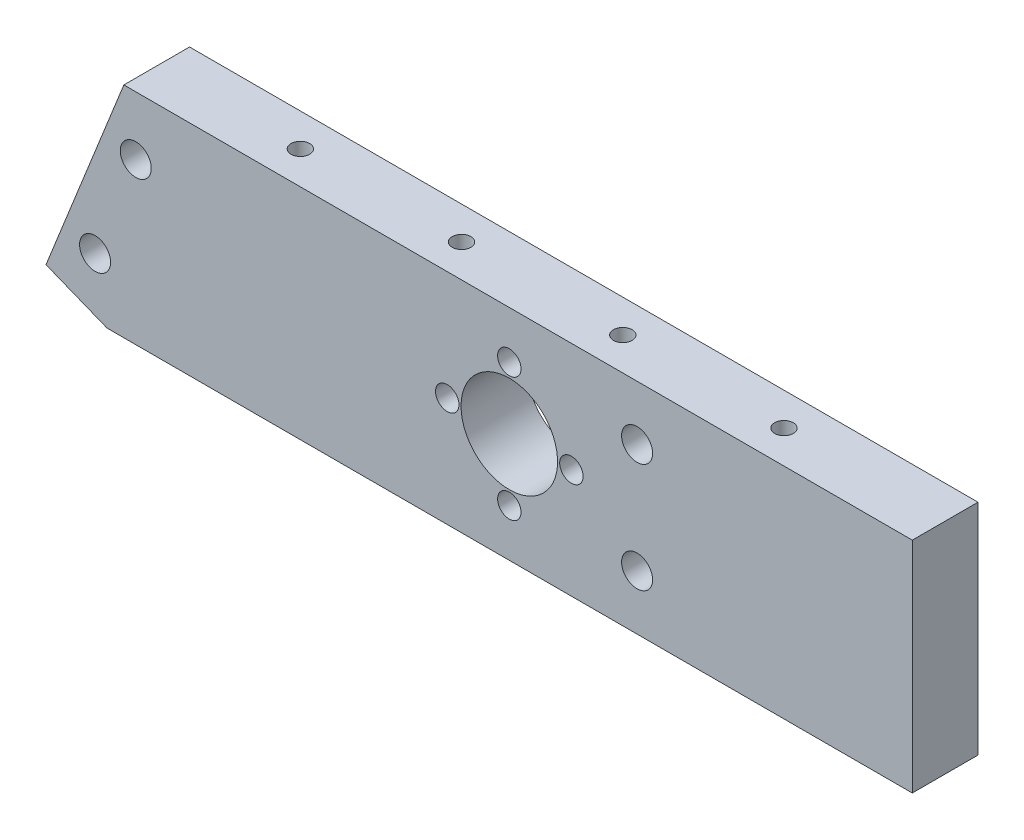
SolidWorks part; units mm, degrees
material "PE High Density"
ref_plane "Front Plane" through (0, 0, 0) normal (0, 0, 1) x (1, 0, 0)
ref_plane "Top Plane" through (0, 0, 0) normal (0, 1, 0) x (1, 0, 0)
ref_plane "Right Plane" through (0, 0, 0) normal (1, 0, 0) x (0, 0, -1)
sketch "Sketch1" plane through (0, 0, 0) normal (0, 0, 1) x (1, 0, 0)
  line L1 (-55.88, 15.875) -> (58.42, 15.875)
  line L2 (-55.88, 15.875) -> (-67.165, -12.3375)
  line L3 (-58.3213, -15.875) -> (58.42, -15.875)
  line L4 (58.42, 15.875) -> (58.42, -15.875)
  line L5 (18.525, 15.875) -> (18.525, -15.875) construction
  line L6 (58.42, 0) -> (-62.23, 0) construction
  line L7 (-62.23, 0) -> (-57.8081, -1.7687) construction
  line L10 (-50.7506, 15.875) -> (-62.7431, -14.1063) construction
  line L11 (-67.165, -12.3375) -> (-58.3213, -15.875)
  circle A0 centre (0, -9) radius 1.7
  circle A1 centre (-9, 0) radius 1.7
  circle A2 centre (0, 9) radius 1.7
  circle A3 centre (9, 0) radius 1.7
  arc A8 (-5.3578, -2.967) -> (-5.3172, -2.9531) centre (-6.35, 0) ccw construction
  circle A16 centre (0, 0) radius 7
  circle A17 centre (0, 0) radius 9 construction
  circle A18 centre (18.525, 7.9375) radius 2.2479
  circle A19 centre (18.525, -7.9375) radius 2.2479
  circle A20 centre (-54.1527, 7.3698) radius 2.2479
  circle A21 centre (-60.0485, -7.3698) radius 2.2479
  point P0 (0, 0)
  point P23 (0, 0)
  dimension "D3" = 3.4
  dimension "D5" = 14
  dimension "D7" = 4.4958
  dimension "D12" = 4.4958
  dimension "D2" = 31.75
  dimension "D8" = 114.3
  dimension "D11" = 9
  dimension "D4" = 58.42
  dimension "D9" = 7.9375
  dimension "D6" = 9.525
  dimension "D10" = 4.7625
  dimension "D13" = 15.875
  dimension "D15" = 9.525
  dimension "D16" = 30.3858
  dimension "D14" = 7.2554
extrude "Boss-Extrude1" add sketch "Sketch1" along normal blind 9.525
hole_wizard "Tap Drill for #6-32 Tap1" positions "Sketch11" profile "Sketch12" hole size "#6-32" standard "ANSI Inch"
sketch "Sketch11" plane through (0, -15.875, 0) normal (0, -1, 0) x (-1, 0, 0)
  line L0 (-58.42, -9.525) -> (-58.42, 0) construction
  line L1 (58.3213, -9.525) -> (-58.42, -9.525) construction
  point P0 (-35.052, -4.7625)
  dimension "D1" = 23.368
  dimension "D2" = 4.7625
sketch "Sketch12" plane through (35.052, -15.875, 4.7625) normal (1, 0, 0) x (0, 0, -1)
  line L0 (0, 0) -> (0, 13.5127)
  line L1 (0, 13.5127) -> (1.3525, 12.7)
  line L2 (1.3525, 12.7) -> (1.3525, 0)
  line L5 (1.3525, 0) -> (0, 0)
  line L10 (0, 13.5127) -> (-1.3526, 12.7) construction
  line L11 (0, -6.35) -> (0, 107.95) construction
  dimension "Hole Dia." = 2.7051
  dimension "Hole Depth" = 12.7
  dimension "Drill Angle" = 118
pattern_linear "LPattern1" count 4 spacing 23.368 along (-1, 0, 0) of "Tap Drill for #6-32 Tap1"
mirror "Mirror8" about plane through (0, 0, 0) normal (0, 1, 0) of "Tap Drill for #6-32 Tap1", "LPattern1"
equation "\"Plate Screw Hole Diameter\"= 0.116in"
equation "\"Plate Width\" = 4.6in"
equation "\"Plate Thickness\" = 0.375in"
equation "\"Num holes\" = 4"
equation "\"Plate Height\" = 1.25in"
equation "\"D1@Sketch11\"=\"Plate Width\" / ( \"Num holes\" + 1)"
equation "\"D2@Sketch11\"=\"Plate Thickness\"/2"
equation "\"D3@LPattern1\"=\"Plate Width\" / ( \"Num holes\"  + 1 )"
equation "\"D2@Sketch1\"=\"Plate Height\""
equation "\"D4@Sketch1\"= \"Plate Width\"/2"
equation "\"Top Plate Width\" = 4.5in"
equation "\"D8@Sketch1\"=\"Top Plate Width\""
equation "\"Plate Clearance Hole Diameter\" = 0.125in"
equation "\"Plate Tap Hole Diameter\" = 0.116in"
equation "\"Bottom Plate Length\" = 6.5in"
equation "\"Number Eight Clearance Size\" = 0.177in"
equation "\"D7@Sketch1\"=\"Number Eight Clearance Size\""
equation "\"D9@Sketch1\"=\"Plate Height\" / 4"
equation "\"D10@Sketch1\"=\"Plate Thickness\"/2"
equation "\"D12@Sketch1\"=\"Number Eight Clearance Size\""
equation "\"D13@Sketch1\"=\"Plate Height\"/2"
equation "\"back_brace_height_offset\"=0.35"
equation "\"D14@Sketch1\"= ( 1.1962912in - 0.625 ) / 2"
